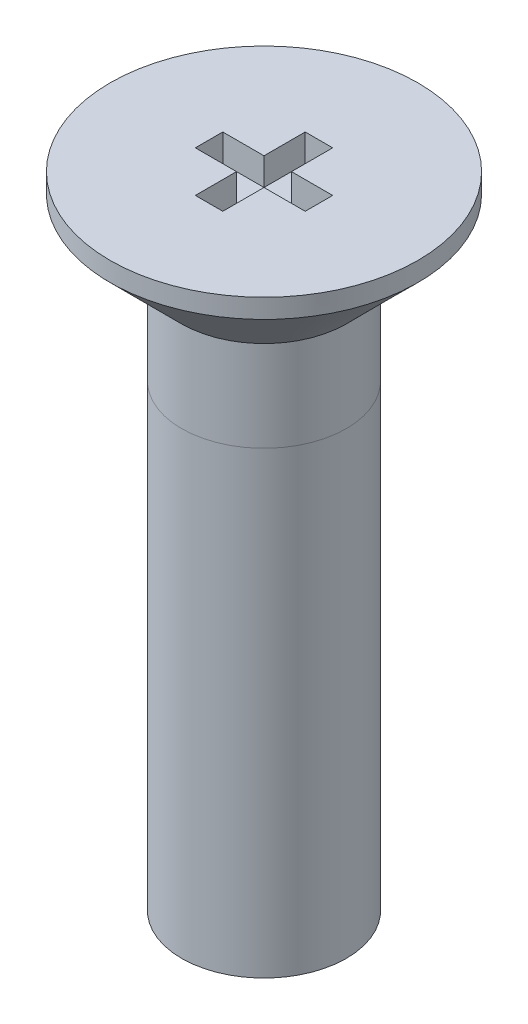
SolidWorks part; units mm, degrees
ref_plane "Front Plane" through (0, 0, 0) normal (0, 0, 1) x (1, 0, 0)
ref_plane "Top Plane" through (0, 0, 0) normal (0, 1, 0) x (1, 0, 0)
ref_plane "Right Plane" through (0, 0, 0) normal (1, 0, 0) x (0, 0, -1)
sketch "Sketch1" plane through (0, 0, 0) normal (0, 1, 0) x (1, 0, 0)
  circle A0 centre (0, 0) radius 1.5
  dimension "D1" = 3
extrude "Boss-Extrude1" add sketch "Sketch1" along normal blind 8.35
sketch "Sketch2" plane through (0, 8.35, 0) normal (0, 1, 0) x (1, 0, 0)
  circle A0 centre (0, 0) radius 1.5
  circle A1 centre (0, 0) radius 1.5 construction
extrude "Boss-Extrude2" add sketch "Sketch2" along normal blind 1.65 separate body
sketch "Sketch3" plane through (0, 10, 0) normal (0, 1, 0) x (1, 0, 0)
  circle A0 centre (0, 0) radius 2.8
  dimension "D1" = 5.6
extrude "Boss-Extrude3" add sketch "Sketch3" along normal blind 1.65
sketch "Sketch6" plane through (0, 0, 0) normal (0, 0, 1) x (1, 0, 0)
  line L0 (1.5, 10) -> (2.8, 11.3)
  line L2 (0, 0) -> (0, 11.65) construction
  line L3 (2.8, 11.65) -> (-2.8, 11.65) construction
  line L4 (2.8, 10) -> (2.8, 11.65) construction
  line L5 (-2.8, 10) -> (2.8, 10) construction
  line L6 (1.5, 10) -> (2.8, 10)
  line L7 (2.8, 10) -> (2.8, 11.3)
  dimension "D1" = 45
revolve "Cut-Revolve1" cut sketch "Sketch6" angle 360 about L2 region at (2.3667, 10.4333, 0)
sketch "Sketch7" plane through (0, 11.65, 0) normal (0, 1, 0) x (1, 0, 0)
  line L0 (0, 1) -> (0, -1) construction
  line L1 (-1, 0) -> (1, 0) construction
  line L3 (-0.25, 1) -> (0.25, 1)
  line L4 (-0.25, 1) -> (-0.25, -1)
  line L5 (-0.25, -1) -> (0.25, -1)
  line L6 (0.25, 1) -> (0.25, -1)
  line L7 (-1, 0.25) -> (1, 0.25)
  line L8 (-1, 0.25) -> (-1, -0.25)
  line L9 (-1, -0.25) -> (1, -0.25)
  line L10 (1, 0.25) -> (1, -0.25)
  circle A0 centre (0, 0) radius 2.8 construction
  dimension "D1" = 1
  dimension "D2" = 0.5
extrude "Cut-Extrude2" cut sketch "Sketch7" against normal blind 0.5 contours L4 L7 L6 L3 | L4 L9 L6 L7 | L10 L7 L6 L9 | L9 L4 L5 L6 | L8 L9 L4 L7 region at (0, 11.65, -0.625) region at (0, 11.65, 0) region at (-0.625, 11.65, 0) region at (0.625, 11.65, 0) region at (0, 11.65, 0.625)
